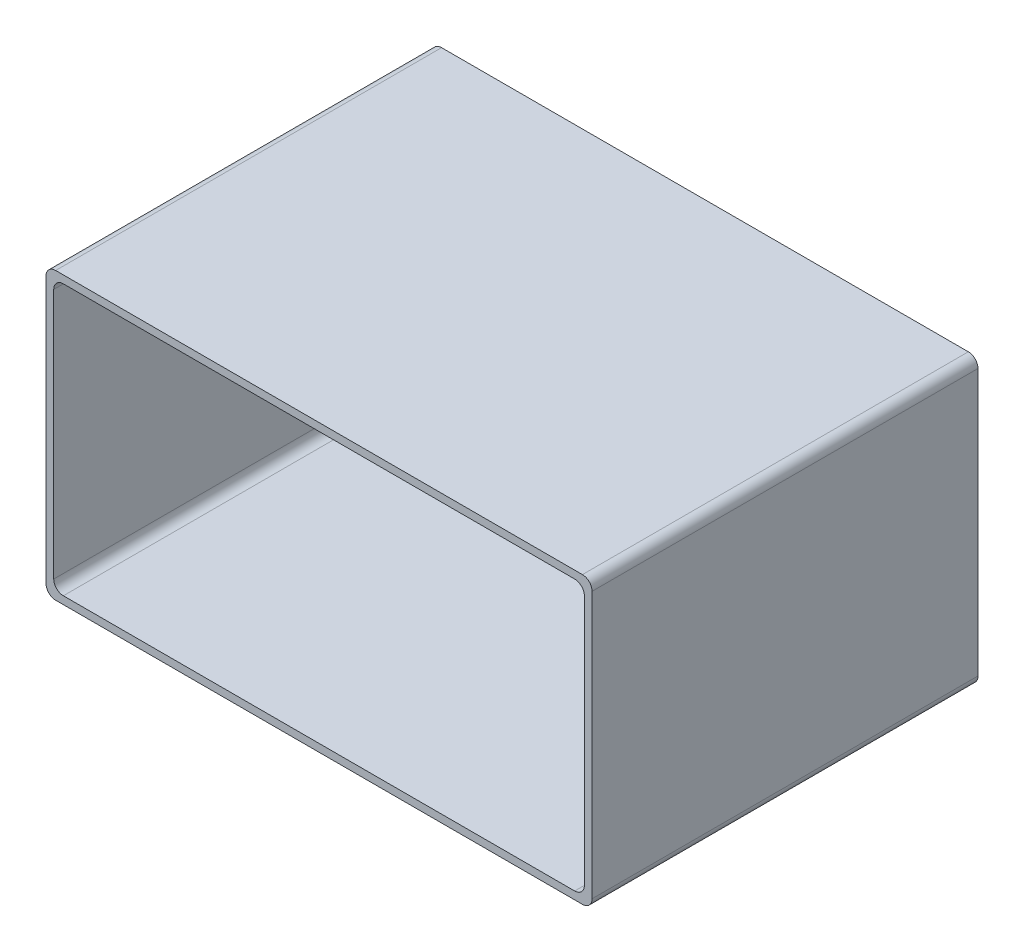
SolidWorks part; units mm, degrees
ref_plane "Plan de face" through (0, 0, 0) normal (0, 0, 1) x (1, 0, 0)
ref_plane "Plan de dessus" through (0, 0, 0) normal (0, 1, 0) x (1, 0, 0)
ref_plane "Plan de droite" through (0, 0, 0) normal (1, 0, 0) x (0, 0, -1)
sketch "Esquisse1" plane through (0, 0, 0) normal (0, 0, 1) x (1, 0, 0)
  line L0 (-28.3, 14.8) -> (28.3, 14.8)
  line L1 (-27.5, 14) -> (27.5, 14)
  line L2 (-27.5, 14) -> (-27.5, -14)
  line L3 (-27.5, -14) -> (27.5, -14)
  line L4 (27.5, 14) -> (27.5, -14)
  line L5 (-27.5, 14) -> (27.5, -14) construction
  line L6 (-27.5, -14) -> (27.5, 14) construction
  line L7 (28.3, 14.8) -> (28.3, -14.8)
  line L8 (-28.3, -14.8) -> (28.3, -14.8)
  line L9 (-28.3, 14.8) -> (-28.3, -14.8)
  point P0 (0, 0)
  dimension "D1" = 28
  dimension "D2" = 55
  dimension "D3" = 0.8
extrude "Boss.-Extru.1" add sketch "Esquisse1" along normal blind 40
fillet "Congé1" radius 1 8 edges at (-27.5, 14, 20) (-27.5, -14, 20) (27.5, -14, 20) (27.5, 14, 20) (28.3, -14.8, 20) (-28.3, -14.8, 20) (-28.3, 14.8, 20) (28.3, 14.8, 20)
